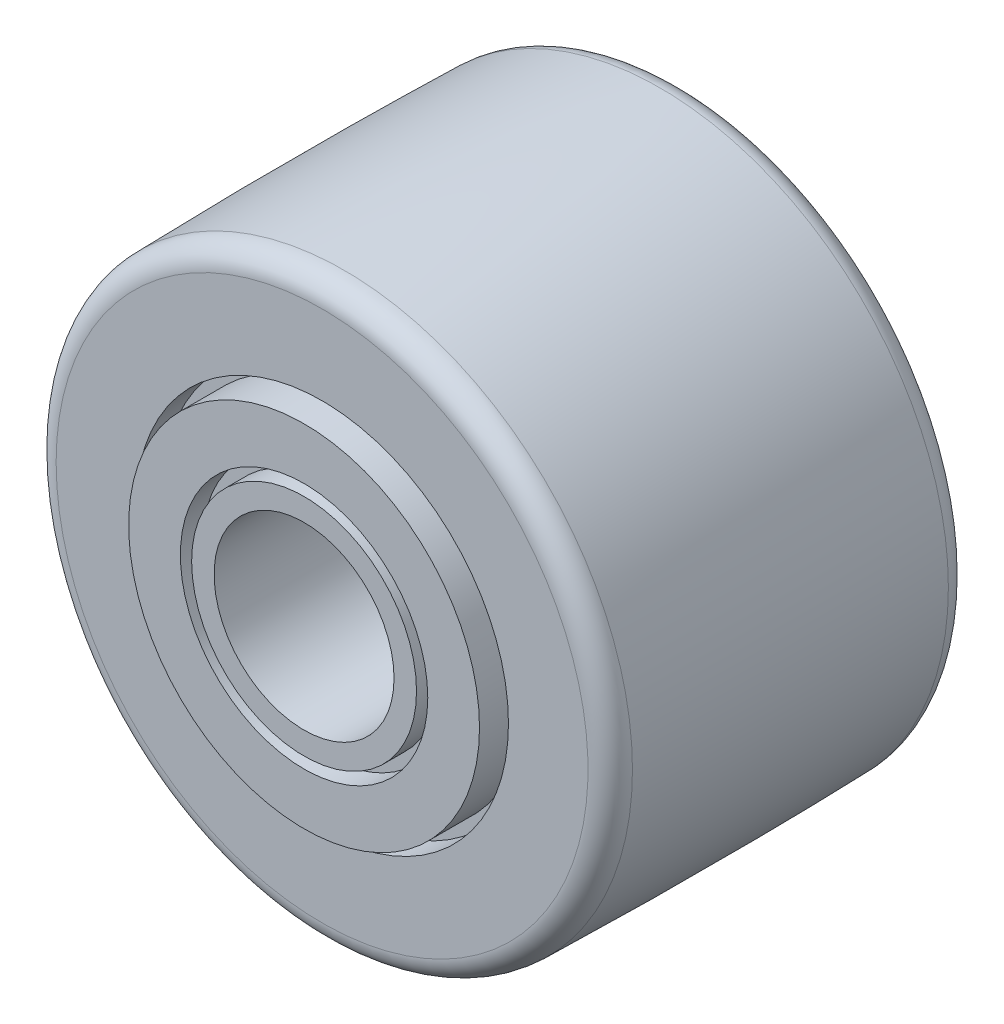
SolidWorks part; units mm, degrees
ref_plane "Front" through (0, 0, 0) normal (0, 0, 1) x (1, 0, 0)
ref_plane "Top" through (0, 0, 0) normal (0, 1, 0) x (1, 0, 0)
ref_plane "Right" through (0, 0, 0) normal (1, 0, 0) x (0, 0, -1)
sketch "Sketch1" plane through (0, 0, 0) normal (1, 0, 0) x (0, 0, -1)
  line L0 (0, 7.7391) -> (0.7938, 7.7391)
  line L1 (17.4625, 7.7391) -> (17.4625, -7.7391) construction
  line L2 (0.7937, 12.7) -> (0.7938, 7.7391)
  line L3 (0.7937, 12.7) -> (16.6687, 12.7) construction
  line L4 (16.6687, 12.7) -> (16.6687, 7.7391)
  line L5 (0, 7.7391) -> (0, -7.7391) construction
  line L6 (16.6687, 7.7391) -> (17.4625, 7.7391)
  line L7 (0, 0) -> (17.4625, 0)
  line L8 (16.6687, -7.7391) -> (17.4625, -7.7391) construction
  line L9 (16.6687, -12.7) -> (16.6687, -7.7391) construction
  line L10 (0.7938, -12.7) -> (16.6687, -12.7) construction
  line L11 (0.7938, -12.7) -> (0.7938, -7.7391) construction
  line L12 (0, -7.7391) -> (0.7938, -7.7391) construction
  line L13 (17.4625, 7.7391) -> (17.4625, 0)
  line L14 (0, 7.7391) -> (0, 0)
  line L15 (8.7312, 12.8034) -> (8.7312, -12.7) construction
  arc A0 (0.7937, 12.7) -> (16.6687, 12.7) centre (8.7312, -291.9966) cw
  point P3 (0.9922, 0)
  point P15 (1.9844, 0)
  dimension "R Crown Radius" = 304.8
  dimension "D1" = 0.9922
  dimension "G O'all Wd." = 17.4625
  dimension "B Roller Width" = 15.875
  dimension "D2" = 1.9844
  dimension "A Roller Dia" = 25.4
  dimension "H Min Clamping Dia" = 15.4781
revolve "Revolve1" add sketch "Sketch1" angle 360 mid plane about L7
sketch "Sketch2" plane through (0, 0, 0) normal (0, 0, 1) x (1, 0, 0)
  circle A0 centre (0, 0) radius 3.9688
  dimension "F Bore ID" = 7.9375
extrude "Cut-Extrude1" cut sketch "Sketch2" against normal through all
sketch "Sketch3" plane through (0, 0, 0) normal (0, 0, 1) x (1, 0, 0)
  circle A0 centre (0, 0) radius 4.9609
  circle A1 centre (0, 0) radius 5.457
  circle A2 centre (0, 0) radius 3.9688 construction
  dimension "D1" = 0.9922
  dimension "D2" = 0.4961
extrude "Cut-Extrude2" cut sketch "Sketch3" against normal up to vertex (0.9922 mm away) up to point (0, 0, -0.9922)
sketch "Sketch4" plane through (0, 0, -0.7938) normal (0, 0, 1) x (1, 0, 0)
  circle A1 centre (0, 0) radius 8.2228
  circle A2 centre (0, 0) radius 7.7391
  circle A3 centre (0, 0) radius 7.7391
  dimension "D2" = 0.4837
  dimension "D1" = 0
extrude "Cut-Extrude3" cut sketch "Sketch4" against normal up to vertex up to point (0, 0, -1.9844)
fillet "Fillet1" radius 0.9922 2 edges at (12.7, 0, -16.6687) (12.7, 0, -0.7937)
ref_plane "Plane1" through (0, 0, -8.7312) normal (0, 0, 1) x (1, 0, 0)
mirror "Mirror1" about plane through (0, 0, -8.7312) normal (0, 0, 1) of "Cut-Extrude3", "Cut-Extrude2"
equation "\"D1@Sketch3\" = \"F Bore ID@Sketch2\" * .125"
equation "\"D2@Sketch3\" = \"D1@Sketch3\" * .5"
equation "\"D1@Sketch1\" = \"B Roller Width@Sketch1\" * .0625"
equation "\"D2@Sketch4\" = \"H Min Clamping Dia@Sketch1\" * .03125"
equation "\"D2@Sketch1\" = \"B Roller Width@Sketch1\"*.125"
equation "\"D1@Fillet1\" = \"B Roller Width@Sketch1\" * .0625"
